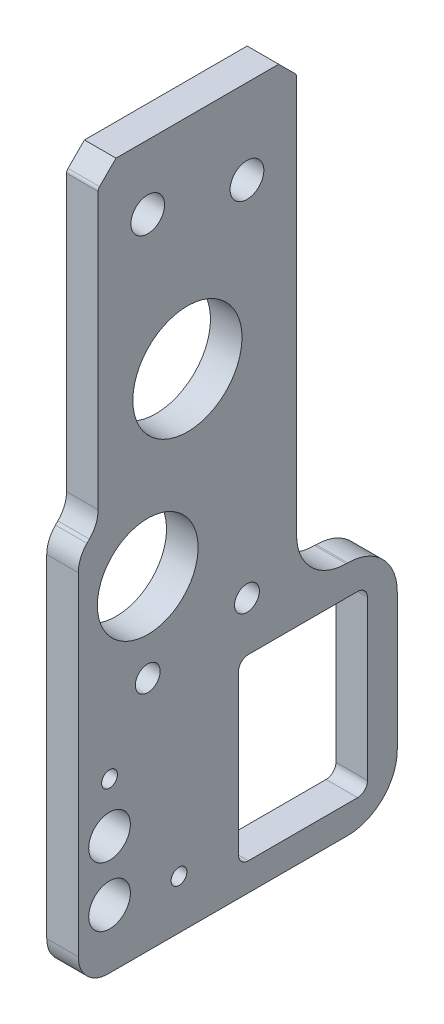
SolidWorks part; units mm, degrees
material "6061 Alloy"
ref_plane "Front Plane" through (0, 0, 0) normal (0, 0, 1) x (1, 0, 0)
ref_plane "Top Plane" through (0, 0, 0) normal (0, 1, 0) x (1, 0, 0)
ref_plane "Right Plane" through (0, 0, 0) normal (1, 0, 0) x (0, 0, -1)
sketch "Sketch1" plane through (0, 0, 0) normal (1, 0, 0) x (0, 0, -1)
  line L2 (0, 0) -> (0, 37.775)
  line L3 (0, 37.775) -> (2, 39.775)
  line L4 (2, 39.775) -> (2, 70.81)
  line L5 (2, 70.81) -> (22, 70.81)
  line L14 (-6.9356, -2) -> (62.4069, -2) construction
  line L15 (7, 37.775) -> (0, 37.775) construction
  line L23 (22, 70.81) -> (22, 23.81)
  line L31 (22, 23.81) -> (32.15, 23.81)
  line L32 (32.15, 23.81) -> (32.15, 0)
  line L33 (32.15, 0) -> (0, 0)
  line L35 (22.65, 20.81) -> (22.65, 2.81) construction
  line L36 (16.15, 20.81) -> (29.15, 20.81)
  line L37 (16.15, 20.81) -> (16.15, 2.81)
  line L38 (16.15, 2.81) -> (29.15, 2.81)
  line L39 (29.15, 20.81) -> (29.15, 2.81)
  circle A0 centre (7, 32.7) radius 5.075
  circle A1 centre (7, 64.31) radius 1.7
  circle A2 centre (17, 62.31) radius 1.7
  circle A5 centre (3.15, 5.95) radius 2.1
  circle A6 centre (3.15, 11.95) radius 2.1
  circle A9 centre (10.15, 4.95) radius 0.8
  circle A10 centre (3.15, 16.95) radius 0.8
  point P1 (7, 23.81)
  point P2 (17, 25.81)
  dimension "D11" = 10.15
  dimension "D13" = 3.4
  dimension "D17" = 15
  dimension "D21" = 2
  dimension "D33" = 4.2
  dimension "D36" = 1.6
  dimension "D4" = 18
  dimension "D5" = 13
  dimension "D22" = 15.75
  dimension "D6" = 16.15
  dimension "D7" = 5
  dimension "D8" = 2
  dimension "D9" = 2
  dimension "D10" = 47
  dimension "D12" = 34.7
  dimension "D14" = 8.5
  dimension "D15" = 6.5
  dimension "D16" = 5
  dimension "D18" = 38.11
  dimension "D19" = 3
  dimension "D20" = 3
  dimension "D23" = 7
  dimension "D24" = 20
  dimension "D25" = 5
  dimension "D28" = 2
  dimension "D30" = 6
  dimension "D32" = 3.15
  dimension "D38" = 12
extrude "Boss-Extrude1" add sketch "Sketch1" along normal blind 3.18
sketch "Sketch3" plane through (0, 0, 0) normal (-1, 0, 0) x (0, 0, 1)
  line L4 (-2, 70.81) -> (-2, 39.775) construction
  circle A0 centre (-11, 48.8109) radius 5.5
  circle A6 centre (-7, 32.7) radius 5.075 construction
  dimension "D1" = 11
  dimension "D3" = 16.6
  dimension "D2" = 9
extrude "Cut-Extrude4" cut sketch "Sketch3" against normal through all
sketch "Sketch8" [suppressed] plane through (3.18, 0, 0) normal (1, 0, 0) x (0, 0, -1)
  line L0 (2, 70.81) -> (2, 39.775) construction
  line L1 (11, 48.8109) -> (2, 48.8109) construction
  line L2 (2, 52.8109) -> (3.5, 52.8109)
  line L3 (3.5, 44.8109) -> (2, 44.8109)
  line L4 (2, 44.8109) -> (2, 52.8109)
  arc A0 (3.5, 44.8109) -> (3.5, 52.8109) centre (11, 48.8109) ccw
  circle A1 centre (7, 32.7) radius 5.075 construction
  point P11 (2, 48.8109)
  dimension "D1" = 16.6
  dimension "D2" = 17
  dimension "D3" = 9
  dimension "D4" = 8
extrude "Cut-Extrude5" [suppressed] cut sketch "Sketch8" against normal through all
fillet "Fillet2" radius 3 3 edges at (1.59, 37.775, 0) (1.59, 39.775, -2) (1.59, 0, 0)
fillet "Chamfer2" radius 1.8 2 edges at (1.59, 70.81, -22) (1.59, 70.81, -2) profile chamfer
fillet "Fillet4" radius 0.5 2 edges at (1.59, 69.01, -2) (1.59, 69.01, -22)
fillet "Fillet5" [suppressed] radius 0.3
sketch "BallRef" plane through (0, 0, 0) normal (-1, 0, 0) x (0, 0, 1)
  line L0 (-31.524, -10.56) -> (65.6624, -10.56) construction
  line L1 (-0.75, 32.7) -> (-0.75, 29.3885) construction
  line L2 (-0.75, 29.3885) -> (31.3703, 29.3885) construction
  line L3 (31.3703, 10.85) -> (31.3703, 29.3885) construction
  line L4 (1.092, -10.56) -> (-13.908, 4.44) construction
  line L5 (-13.908, 4.44) -> (-13.908, -10.56) construction
  line L6 (-13.908, -10.56) -> (1.092, -10.56) construction
  circle A0 centre (-7, 32.7) radius 6.25 construction
  circle A1 centre (9.9603, 10.85) radius 21.41 construction
  dimension "D1" = 12.5
  dimension "D2" = 42.82
  dimension "D3" = 43.26
  dimension "D4" = 45
  dimension "D5" = 15
hole_wizard "M2 Tapped Hole1" positions "3DSketch1" profile "Sketch12" tap size "M2" standard "AS" end condition through all
sketch3d "3DSketch1"
  line L0 (3.18, 16.95, -3.15) -> (0, 16.95, -3.15) construction
  line L1 (3.18, 4.95, -10.15) -> (0, 4.95, -10.15) construction
  point P0 (0, 16.95, -3.15)
  point P4 (0, 4.95, -10.15)
sketch "Sketch12" plane through (0, 16.95, -3.15) normal (0, 1, 0) x (0, 0, 1)
  line L0 (0, 0) -> (0, 3.18)
  line L1 (0, 3.18) -> (0.8, 3.18)
  line L2 (0.8, 3.18) -> (0.8, 0)
  line L5 (0.8, 0) -> (0, 0)
  line L11 (0, -6.35) -> (0, 107.95) construction
  dimension "Thru Tap Drill Dia." = 1.6
  dimension "Thru Tap Drill Depth" = 3.18
cosmetic thread "Hole Thread3" parameters "D2"=2
cosmetic thread "Hole Thread4" parameters "D2"=2
fillet "Fillet9" radius 1 4 edges at (1.59, 2.81, -29.15) (1.59, 2.81, -16.15) (1.59, 20.81, -29.15) (1.59, 20.81, -16.15)
fillet "Fillet11" radius 5 3 edges at (1.59, 0, -32.15) (1.59, 23.81, -22) (1.59, 23.81, -32.15)
hole_wizard "M3x0.5 Tapped Hole1" positions "Sketch13" profile "Sketch14" tap size "M3x0.5" standard "ANSI Metric" end condition through all
sketch "Sketch13" plane through (3.18, 0, 0) normal (1, 0, 0) x (0, 0, -1)
  point P0 (7, 23.81)
  point P3 (17, 25.81)
cosmetic thread "Hole Thread5" parameters "D2"=3
cosmetic thread "Hole Thread6" parameters "D2"=3
sketch "Sketch14" plane through (3.18, 23.81, -7) normal (0, 1, 0) x (0, 0, -1)
  line L0 (0, 0) -> (0, 3.18)
  line L1 (0, 3.18) -> (1.25, 3.18)
  line L2 (1.25, 3.18) -> (1.25, 0)
  line L5 (1.25, 0) -> (0, 0)
  line L11 (0, -6.35) -> (0, 107.95) construction
  dimension "Thru Tap Drill Dia." = 2.5
  dimension "Thru Tap Drill Depth" = 3.18
equation "\"7.5.00mm\"=5"
